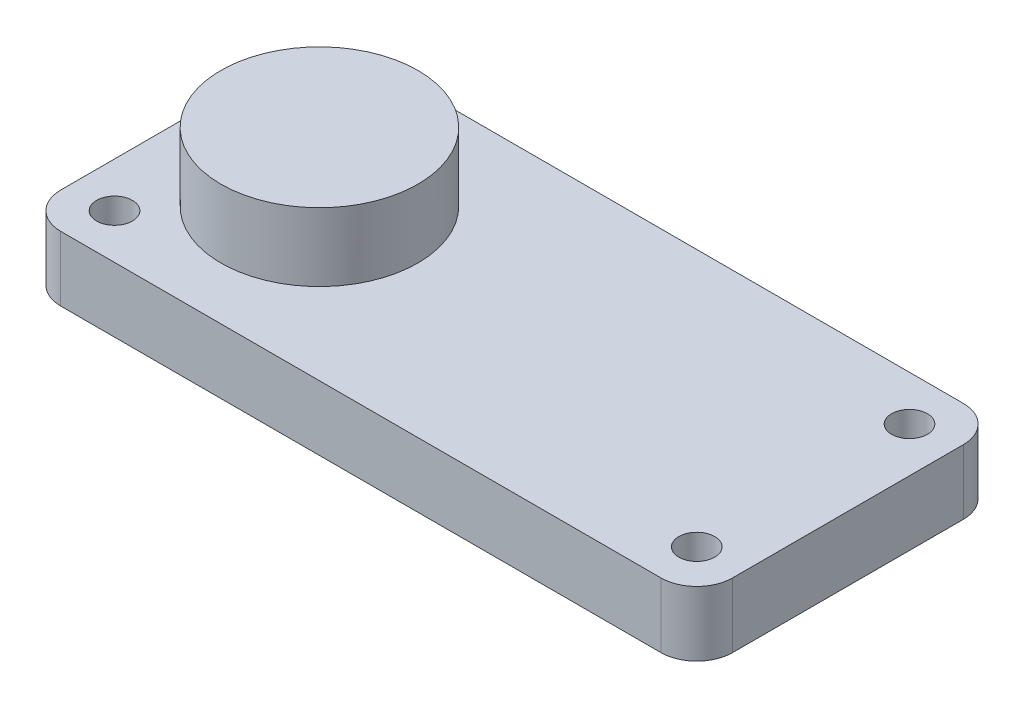
SolidWorks part; units mm, degrees
ref_plane "Front Plane" through (0, 0, 0) normal (0, 0, 1) x (1, 0, 0)
ref_plane "Top Plane" through (0, 0, 0) normal (0, 1, 0) x (1, 0, 0)
ref_plane "Right Plane" through (0, 0, 0) normal (1, 0, 0) x (0, 0, -1)
sketch "Sketch2" plane through (0, 0, 0) normal (0, 1, 0) x (1, 0, 0)
  line L1 (-26.8, -13.5) -> (26.8, -13.5)
  line L2 (-30, -10.3) -> (-30, 10.3)
  line L3 (-26.8, 13.5) -> (26.8, 13.5)
  line L4 (30, -10.3) -> (30, 10.3)
  line L5 (-30, -13.5) -> (30, 13.5) construction
  line L6 (-30, 13.5) -> (30, -13.5) construction
  line L7 (-26, -9.5) -> (26, -9.5) construction
  line L8 (-26, -9.5) -> (-26, 9.5) construction
  line L9 (-26, 9.5) -> (26, 9.5) construction
  line L10 (26, -9.5) -> (26, 9.5) construction
  line L11 (-26, -9.5) -> (26, 9.5) construction
  line L12 (-26, 9.5) -> (26, -9.5) construction
  circle A0 centre (26, 9.5) radius 1.6
  circle A1 centre (-26, 9.5) radius 1.6
  circle A2 centre (-26, -9.5) radius 1.6
  circle A3 centre (26, -9.5) radius 1.6
  arc A4 (26.8, 13.5) -> (30, 10.3) centre (26.8, 10.3) cw
  arc A5 (26.8, -13.5) -> (30, -10.3) centre (26.8, -10.3) ccw
  arc A6 (-26.8, -13.5) -> (-30, -10.3) centre (-26.8, -10.3) cw
  arc A7 (-30, 10.3) -> (-26.8, 13.5) centre (-26.8, 10.3) cw
  point P0 (0, 0)
  point P6 (0, 0)
  dimension "D1" = 3.2
extrude "Boss-Extrude1" add sketch "Sketch2" along normal blind 5.78
sketch "Sketch3" plane through (0, 5.78, 0) normal (0, 1, 0) x (1, 0, 0)
  line L0 (-26, 9.5) -> (-26, -9.5) construction
  line L1 (-1000, 0) -> (49000, 0) construction
  line L2 (-26, 0) -> (-17.2, 0) construction
  circle A0 centre (-26, 9.5) radius 1.6 construction
  circle A1 centre (-26, -9.5) radius 1.6 construction
  circle A2 centre (-17.2, 0) radius 8.8
  point P8 (-26, 0)
extrude "Boss-Extrude2" add sketch "Sketch3" along normal blind 6.1 contours A2
